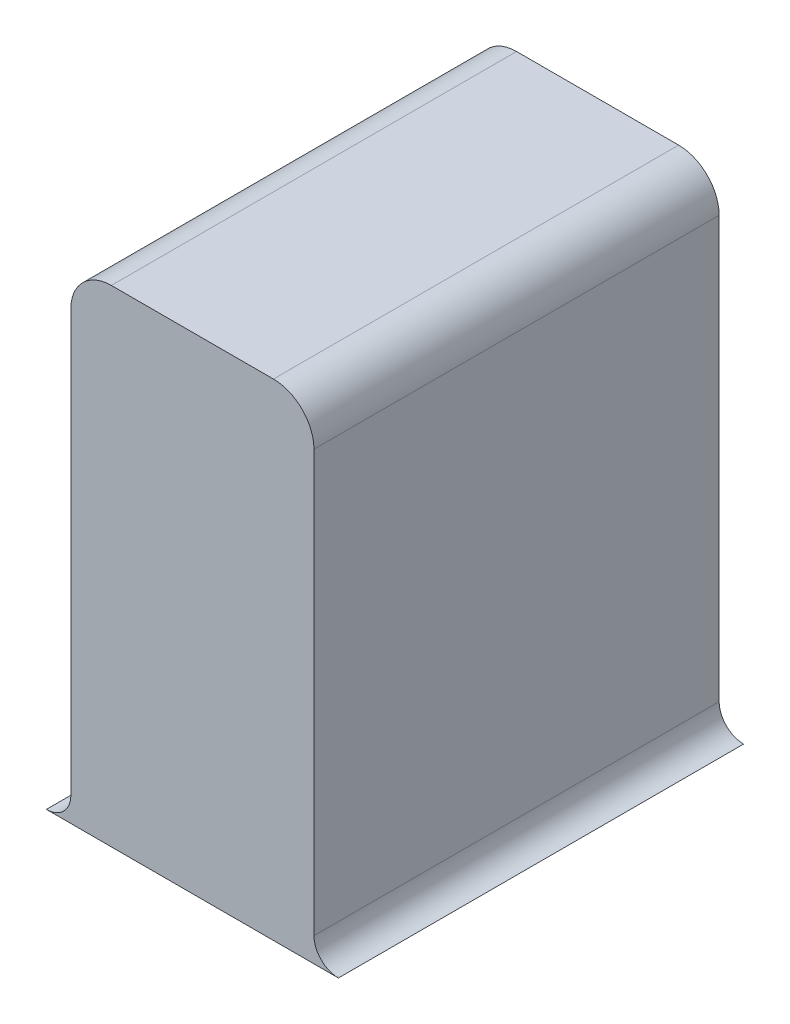
SolidWorks part; units mm, degrees
ref_plane "Plano frontal" through (0, 0, 0) normal (0, 0, 1) x (1, 0, 0)
ref_plane "Plano superior" through (0, 0, 0) normal (0, 1, 0) x (1, 0, 0)
ref_plane "Plano direito" through (0, 0, 0) normal (1, 0, 0) x (0, 0, -1)
sketch "Esboço1" plane through (0, 0, 0) normal (0, 0, 1) x (1, 0, 0)
  line L0 (-4, -37.8704) -> (-4.3019, -37.8704)
  line L1 (-2.5, -37.8704) -> (-2.5, -31.8704)
  line L3 (-2.5, -31.8704) -> (-4, -31.8704)
  line L4 (-2.5, -31.8704) -> (-2.5, -37.8704)
  line L5 (-2.5, -37.8704) -> (-4, -37.8704)
  line L6 (-4, -31.8704) -> (-4, -37.8704)
  line L7 (-2.5, -31.8704) -> (-1, -31.8704)
  line L8 (-2.5, -31.8704) -> (-2.5, -37.8704)
  line L9 (-2.5, -37.8704) -> (-1, -37.8704)
  line L10 (-1, -31.8704) -> (-1, -37.8704)
  line L11 (-4, -37.8704) -> (-4, -37.5685)
  line L12 (-0.6981, -37.8704) -> (-1, -37.8704)
  arc A0 (-4.3019, -37.8704) -> (-4, -37.5685) centre (-4.3019, -37.5685) ccw
  arc A1 (-0.6981, -37.8704) -> (-1, -37.5685) centre (-0.6981, -37.5685) cw
  dimension "D1" = 1.5
  dimension "D2" = 1.5
  dimension "D3" = 6
extrude "Ressalto-extrusão1" add sketch "Esboço1" along normal blind 5 contours L3 L6 L5 L1 | L10 L7 L1 L9 region at (-3.25, -34.8704, 0) region at (-1.75, -34.8704, 0)
fillet "Filete1" radius 0.5 2 edges at (-1, -31.8704, 2.5) (-4, -31.8704, 2.5)
extrude "Ressalto-extrusão2" add sketch "Esboço1<5>" along normal through all contours L12 A1 L10 | A0 L0 L6 region at (-4.0674, -37.8029, 0) region at (-0.9326, -37.8029, 0)
sketch "Esboço1<5>" plane through (0, 0, 0) normal (0, 0, 1) x (1, 0, 0) same geometry as "Esboço1"
